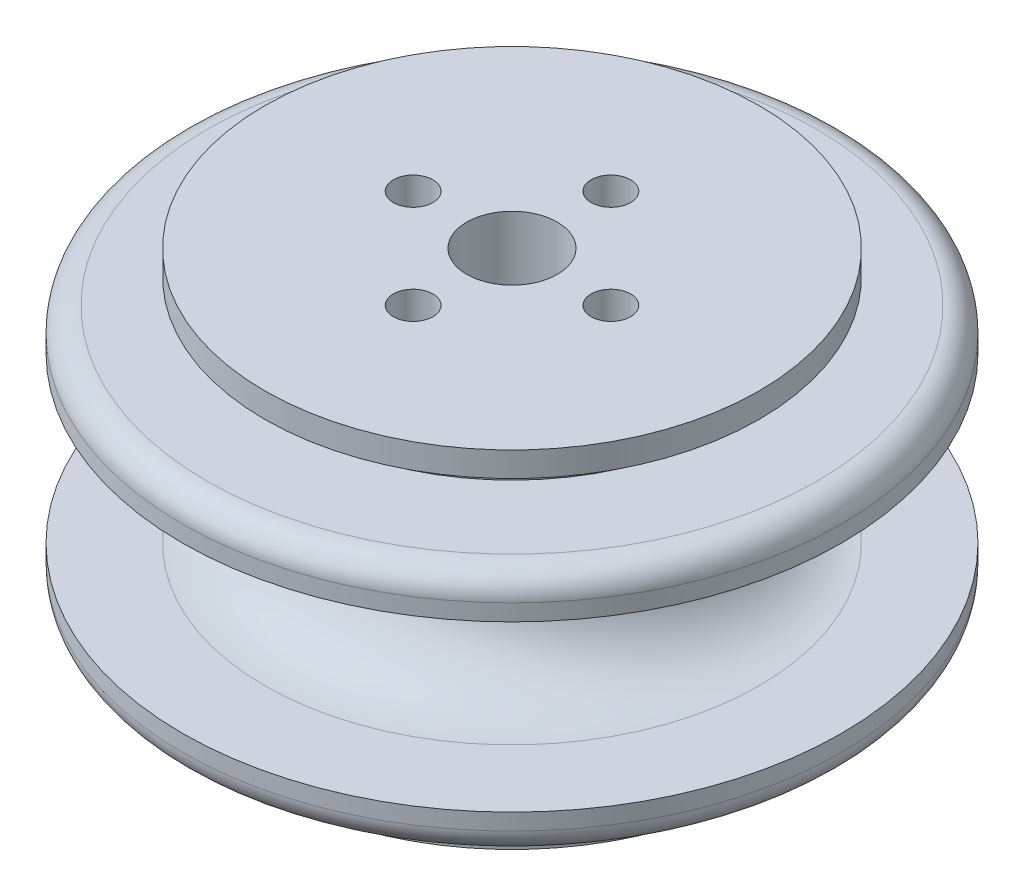
SolidWorks part; units mm, degrees
ref_plane "前视基准面" through (0, 0, 0) normal (0, 0, 1) x (1, 0, 0)
ref_plane "上视基准面" through (0, 0, 0) normal (0, 1, 0) x (1, 0, 0)
ref_plane "右视基准面" through (0, 0, 0) normal (1, 0, 0) x (0, 0, -1)
other "Configuration Table"
sketch "草图1" plane through (0, 0, 0) normal (0, 1, 0) x (1, 0, 0)
  circle A0 centre (0, 0) radius 40
  dimension "D1" = 80
extrude "凸台-拉伸1" add sketch "草图1" along normal blind 30
sketch "草图2" plane through (0, 30, 0) normal (0, 1, 0) x (1, 0, 0)
  circle A0 centre (0, 0) radius 26
  dimension "D1" = 52
extrude "凸台-拉伸2" add sketch "草图2" along normal blind 3
sketch "草图3" plane through (0, 33, 0) normal (0, 1, 0) x (1, 0, 0)
  circle A0 centre (0, 0) radius 30
  dimension "D1" = 60
extrude "凸台-拉伸3" add sketch "草图3" along normal blind 3
fillet "圆角1" radius 1 1 edges at (0, 33, 26)
ref_plane "基准面1" through (0, 15, 0) normal (0, 1, 0) x (1, 0, 0)
mirror "镜向1" about plane through (0, 15, 0) normal (0, 1, 0) of "圆角1", "凸台-拉伸3", "凸台-拉伸2"
sketch "草图4" plane through (0, 0, 0) normal (0, 0, 1) x (1, 0, 0)
  line L3 (-40, 25) -> (-20, 25)
  line L4 (-20, 5) -> (-20, 25)
  line L5 (-40, 5) -> (-20, 5)
  line L6 (0, -1000) -> (0, 49000) construction
  line L7 (-26, 0) -> (26, 0) construction
  line L8 (-40, 25) -> (-40, 5)
  point P13 (0, 0)
  dimension "D1" = 20
revolve "切除-旋转1" cut sketch "草图4" angle 360 about L6
fillet "圆角2" radius 10 2 edges at (20, 5, 0) (20, 25, 0)
fillet "圆角3" radius 3 1 edges at (0, 0, 40)
fillet "圆角4" radius 3 1 edges at (0, 30, 40)
sketch "草图5" plane through (0, 36, 0) normal (0, 1, 0) x (1, 0, 0)
  circle A0 centre (0, 0) radius 5.5
  circle A1 centre (0, 0) radius 12
  circle A2 centre (0, 12) radius 2.4
  circle A3 centre (12, 0) radius 2.4
  circle A4 centre (0, -12) radius 2.4
  circle A5 centre (-12, 0) radius 2.4
  point P15 (0, 0)
  dimension "D1" = 11
  dimension "D2" = 24
  dimension "D3" = 4.8
  dimension "D4" = 4
extrude "切除-拉伸1" cut sketch "草图5" against normal through all contours A0 | A1 A4 | A5 | A4 | A3 | A2 region at (0, 36, 0) region at (0, 36, 10.9394)
